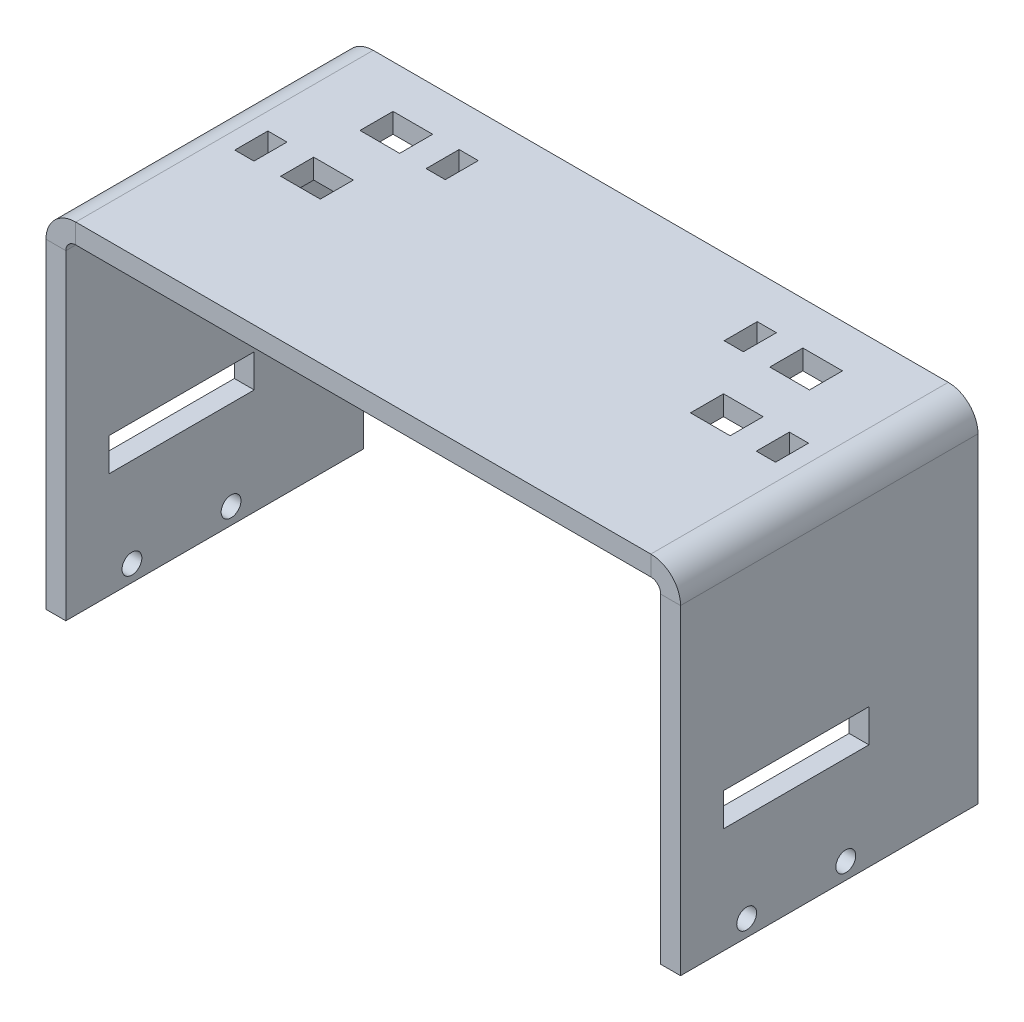
SolidWorks part; units mm, degrees
ref_plane "Front Plane" through (0, 0, 0) normal (0, 0, 1) x (1, 0, 0)
ref_plane "Top Plane" through (0, 0, 0) normal (0, 1, 0) x (1, 0, 0)
ref_plane "Right Plane" through (0, 0, 0) normal (1, 0, 0) x (0, 0, -1)
sketch "Sketch1" plane through (0, 0, 0) normal (0, 1, 0) x (1, 0, 0)
  line L2 (-95, 31.9466) -> (-95, -13.0534)
  line L3 (-95, -13.0534) -> (95, -13.0534) construction
  line L4 (95, 31.9466) -> (95, -13.0534)
  line L9 (34, 8.4466) -> (28, 13.4466) construction
  line L22 (-40.9, 15.9056) -> (-38, 15.9056) construction
  line L23 (-40.9, 15.9056) -> (-40.9, 5.9056) construction
  line L28 (-40.9, 5.9056) -> (-38, 5.9056) construction
  line L29 (-38, 15.9056) -> (-38, 5.9056) construction
  line L34 (-40.9, 15.9056) -> (-38, 5.9056) construction
  line L35 (-40.9, 5.9056) -> (-38, 15.9056) construction
  line L40 (-34, 29.4466) -> (-28, 29.4466) construction
  line L41 (-34, 29.4466) -> (-34, 4.4466) construction
  line L42 (-34, 4.4466) -> (-28, 4.4466) construction
  line L43 (-28, 29.4466) -> (-28, 4.4466) construction
  line L44 (-34, 29.4466) -> (-28, 4.4466) construction
  line L45 (-34, 4.4466) -> (-28, 29.4466) construction
  line L46 (-24, 27.9478) -> (-21.1, 27.9478) construction
  line L47 (-24, 27.9478) -> (-24, 17.9478) construction
  line L48 (-24, 17.9478) -> (-21.1, 17.9478) construction
  line L49 (-21.1, 27.9478) -> (-21.1, 17.9478) construction
  line L50 (-24, 27.9478) -> (-21.1, 17.9478) construction
  line L51 (-24, 17.9478) -> (-21.1, 27.9478) construction
  line L52 (-40.9, 13.4056) -> (-38, 13.4056)
  line L53 (-40.9, 13.4056) -> (-40.9, 8.4056)
  line L54 (-40.9, 8.4056) -> (-38, 8.4056)
  line L55 (-38, 13.4056) -> (-38, 8.4056)
  line L56 (-40.9, 13.4056) -> (-38, 8.4056) construction
  line L57 (-40.9, 8.4056) -> (-38, 13.4056) construction
  line L58 (-24, 25.4478) -> (-21.1, 25.4478)
  line L59 (-24, 25.4478) -> (-24, 20.4478)
  line L60 (-24, 20.4478) -> (-21.1, 20.4478)
  line L61 (-21.1, 25.4478) -> (-21.1, 20.4478)
  line L62 (-24, 25.4478) -> (-21.1, 20.4478) construction
  line L63 (-24, 20.4478) -> (-21.1, 25.4478) construction
  line L64 (-34, 25.4466) -> (-28, 25.4466)
  line L65 (-34, 25.4466) -> (-34, 20.4466)
  line L66 (-34, 20.4466) -> (-28, 20.4466)
  line L67 (-28, 25.4466) -> (-28, 20.4466)
  line L68 (-34, 25.4466) -> (-28, 20.4466) construction
  line L69 (-34, 20.4466) -> (-28, 25.4466) construction
  line L70 (-34, 13.4466) -> (-28, 13.4466)
  line L71 (-34, 13.4466) -> (-34, 8.4466)
  line L72 (-34, 8.4466) -> (-28, 8.4466)
  line L73 (-28, 13.4466) -> (-28, 8.4466)
  line L74 (-34, 13.4466) -> (-28, 8.4466) construction
  line L75 (-34, 8.4466) -> (-28, 13.4466) construction
  line L76 (34, 13.4466) -> (28, 8.4466) construction
  line L77 (34, 20.4466) -> (28, 25.4466) construction
  line L78 (34, 25.4466) -> (28, 20.4466) construction
  line L79 (24, 20.4478) -> (21.1, 25.4478) construction
  line L80 (24, 25.4478) -> (21.1, 20.4478) construction
  line L81 (40.9, 8.4056) -> (38, 13.4056) construction
  line L82 (40.9, 13.4056) -> (38, 8.4056) construction
  line L83 (24, 17.9478) -> (21.1, 27.9478) construction
  line L84 (24, 27.9478) -> (21.1, 17.9478) construction
  line L85 (21.1, 27.9478) -> (21.1, 17.9478) construction
  line L86 (24, 17.9478) -> (21.1, 17.9478) construction
  line L87 (24, 27.9478) -> (24, 17.9478) construction
  line L88 (24, 27.9478) -> (21.1, 27.9478) construction
  line L89 (34, 4.4466) -> (28, 29.4466) construction
  line L90 (34, 29.4466) -> (28, 4.4466) construction
  line L91 (28, 29.4466) -> (28, 4.4466) construction
  line L92 (34, 4.4466) -> (28, 4.4466) construction
  line L93 (34, 29.4466) -> (34, 4.4466) construction
  line L94 (34, 29.4466) -> (28, 29.4466) construction
  line L95 (40.9, 5.9056) -> (38, 15.9056) construction
  line L96 (40.9, 15.9056) -> (38, 5.9056) construction
  line L97 (38, 15.9056) -> (38, 5.9056) construction
  line L98 (40.9, 5.9056) -> (38, 5.9056) construction
  line L99 (40.9, 15.9056) -> (40.9, 5.9056) construction
  line L100 (40.9, 15.9056) -> (38, 15.9056) construction
  line L101 (28, 13.4466) -> (28, 8.4466)
  line L102 (34, 8.4466) -> (28, 8.4466)
  line L103 (34, 13.4466) -> (34, 8.4466)
  line L104 (34, 13.4466) -> (28, 13.4466)
  line L105 (28, 25.4466) -> (28, 20.4466)
  line L106 (34, 20.4466) -> (28, 20.4466)
  line L107 (34, 25.4466) -> (34, 20.4466)
  line L108 (34, 25.4466) -> (28, 25.4466)
  line L109 (21.1, 25.4478) -> (21.1, 20.4478)
  line L110 (24, 20.4478) -> (21.1, 20.4478)
  line L111 (24, 25.4478) -> (24, 20.4478)
  line L112 (24, 25.4478) -> (21.1, 25.4478)
  line L113 (38, 13.4056) -> (38, 8.4056)
  line L114 (40.9, 8.4056) -> (38, 8.4056)
  line L115 (40.9, 13.4056) -> (40.9, 8.4056)
  line L116 (40.9, 13.4056) -> (38, 13.4056)
  line L122 (95, -13.0534) -> (-95, -13.0534)
  line L126 (45, 31.9466) -> (-45, 31.9466)
  line L130 (45, 31.9466) -> (95, 31.9466)
  line L131 (-95, 31.9466) -> (-45, 31.9466)
  line L132 (0, -11.5262) -> (0, 31.9466) construction
  line L133 (79, 15.4466) -> (74, 15.4466)
  line L134 (79, 15.4466) -> (79, -6.5534)
  line L135 (79, -6.5534) -> (74, -6.5534)
  line L136 (74, 15.4466) -> (74, -6.5534)
  line L137 (-79, 15.4466) -> (-79, -6.5534)
  line L138 (-74, 15.4466) -> (-74, -6.5534)
  line L139 (-79, -6.5534) -> (-74, -6.5534)
  line L140 (-79, 15.4466) -> (-74, 15.4466)
  circle A0 centre (92.5, -3.0534) radius 1.5
  circle A1 centre (92.5, 11.9466) radius 1.5
  circle A2 centre (-92.5, -3.0534) radius 1.5
  circle A3 centre (-92.5, 11.9466) radius 1.5
  point P0 (0, 0)
  point P6 (-39.45, 10.9056)
  point P11 (-39.45, 10.9056)
  point P12 (-31, 16.9466)
  point P17 (-22.55, 22.9478)
  point P22 (-22.55, 22.9478)
  point P33 (-31, 22.9466)
  point P38 (-31, 10.9466)
  point P71 (31, 10.9466)
  point P72 (31, 22.9466)
  point P73 (22.55, 22.9478)
  point P74 (31, 16.9466)
  point P75 (39.45, 10.9056)
  point P84 (76.5, 15.4466)
  dimension "D27" = 3
  dimension "D28" = 3
  dimension "D2" = 45
  dimension "D3" = 2.9
  dimension "D4" = 21.1
  dimension "D5" = 2.9
  dimension "D6" = 10
  dimension "D7" = 10
  dimension "D8" = 25
  dimension "D9" = 4
  dimension "D10" = 6.5
  dimension "D11" = 4
  dimension "D12" = 95
  dimension "D13" = 5
  dimension "D14" = 5
  dimension "D15" = 5
  dimension "D16" = 5
  dimension "D17" = 6
  dimension "D18" = 6
  dimension "D19" = 95
  dimension "D20" = 6
  dimension "D21" = 6
  dimension "D22" = 50
  dimension "D23" = 50
  dimension "D24" = 16
  dimension "D25" = 10
  dimension "D26" = 15
  dimension "D29" = 2.5
  dimension "D30" = 21
  dimension "D31" = 22
  dimension "D32" = 3.5
  dimension "D33" = 6.5
base flange "Base-Flange1" sketch "Sketch1" thickness 3 reverse thickness direction no parameters "D1"=7.5
sketch "Sketch25" plane through (0, -3, 0) normal (0, -1, 0) x (1, 0, 0)
  line L0 (45, -31.9466) -> (45, 13.0534)
  line L1 (-95, 13.0534) -> (95, 13.0534) construction
  line L2 (-45, -31.9466) -> (-45, 13.0534)
sketched bend "Sketched Bend1" bend radius 1.5 thickness 3 bend on line 2 starts at -1.5 ends at 1.5 away from the fixed side along (-1, 0, 0) bending towards (0, -1, 0) bend on line 1 starts at -1.5 ends at 1.5 away from the fixed side along (1, 0, 0) bending towards (0, -1, 0)
bend "SketchBend1" bend radius 1.5 bend angle 90 parameters "D5"=1
bend "SketchBend2" bend radius 1.5 bend angle 90 parameters "D5"=2
sketch "Sketch30" plane through (0, 0, 0) normal (0, 1, 0) x (1, 0, 0)
  line L0 (0, 31.9466) -> (0, -13.0534) construction
  line L1 (43.5, 31.9466) -> (-43.5, 31.9466) construction
  line L2 (-43.5, -13.0534) -> (43.5, -13.0534) construction
sketch "Bend-Lines3" plane through (0, 0, 0) normal (0, 1, 0) x (1, 0, 0)
sketch "Bounding-Box3" plane through (0, 0, 0) normal (0, 1, 0) x (1, 0, 0)
